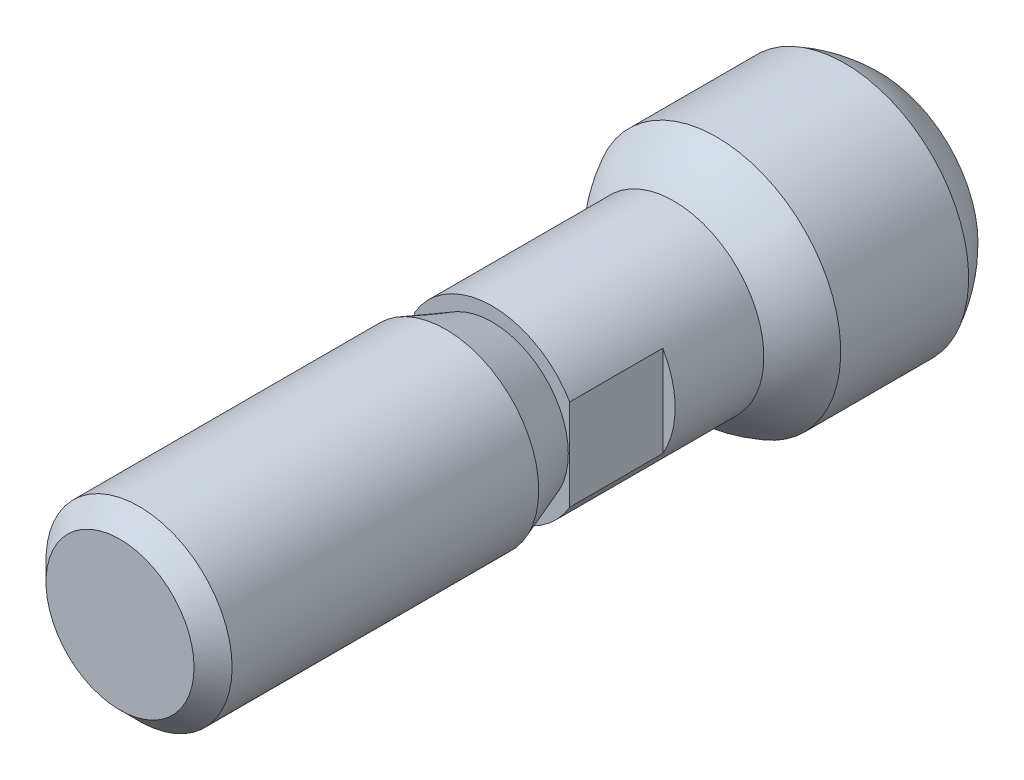
SolidWorks part; units mm, degrees
ref_plane "Ebene vorne" through (0, 0, 0) normal (0, 0, 1) x (1, 0, 0)
ref_plane "Ebene oben" through (0, 0, 0) normal (0, 1, 0) x (1, 0, 0)
ref_plane "Ebene rechts" through (0, 0, 0) normal (1, 0, 0) x (0, 0, -1)
sketch "Skizze1" plane through (0, 0, 0) normal (0, 1, 0) x (1, 0, 0)
  line L0 (0, 0) -> (-2.9, 0)
  line L1 (-2.9, 0) -> (-2.9, 5.8591)
  line L2 (-4, 7.2384) -> (-4, 11.3616)
  line L3 (-3.1639, 12.5) -> (0, 12.5)
  line L4 (0, 12.5) -> (0, 0)
  line L5 (0, 12.5) -> (0, 0) construction
  arc A0 (-2.9, 5.8591) -> (-4, 7.2384) centre (0, 9.3) cw
  arc A1 (-4, 11.3616) -> (-3.1639, 12.5) centre (0, 9.3) cw
revolve "Rotation1" add sketch "Skizze1" angle 360 about L5 reverse direction yes
ref_plane "Ebene1" through (0, 0, 0) normal (0, 0, 1) x (1, 0, 0)
sketch "Skizze2" plane through (0, 0, 0) normal (0, 0, 1) x (1, 0, 0)
  line L0 (6, 4) -> (2.5, 4)
  line L1 (2.5, 4) -> (2.5, -5)
  line L2 (2.5, -5) -> (-2.5, -5)
  line L3 (-2.5, -5) -> (-2.5, 4)
  line L4 (-2.5, 4) -> (-6, 4)
  line L5 (-6, 4) -> (-6, -6)
  line L6 (-6, -6) -> (6, -6)
  line L7 (6, -6) -> (6, 4)
extrude "Schnitt-Linear austragen1" cut sketch "Skizze2" along normal blind 3 and the other way blind 3
sketch "Skizze3" plane through (0, 0, 0) normal (0, 1, 0) x (1, 0, 0)
  line L0 (0, -12) -> (-2.3865, -12)
  line L1 (-2.3865, -12) -> (-3, -11.3865)
  line L2 (-3, -11.3865) -> (-3, -1.5)
  line L3 (-3, -1.5) -> (-2.454, 0)
  line L4 (-2.454, 0) -> (0, 0)
  line L5 (0, 0) -> (0, -12)
  line L6 (0, 0) -> (0, -12) construction
revolve "Rotation2" add sketch "Skizze3" angle 360 about L6 reverse direction yes
cosmetic thread "Gewindedarstellung1" parameters "D1"=10.5, "D2"=4.773
ref_plane "Ebene2" through (0, 0, 3.2) normal (0, 0, 1) x (1, 0, 0)
ref_plane "Ebene3" through (0, 0, 3) normal (0, 0, 1) x (1, 0, 0)
ref_plane "FDT_CYLINDER XY" through (0, 0, 3.2) normal (0, 0, -1) x (-1, 0, 0)
ref_plane "FDT_CYLINDER XZ" through (0, 0, 0) normal (0, 1, 0) x (1, 0, 0)
ref_plane "FDT_CYLINDER YZ" through (0, 0, 0) normal (1, 0, 0) x (0, 0, -1)
ref_axis "FDT_CYLINDER X" through (-80.9, 0, 3.2) along (1, 0, 0)
ref_axis "FDT_CYLINDER Y" through (0, 50, 3.2) along (0, -1, 0)
ref_axis "FDT_CYLINDER Z" through (0, 0, -80.9) along (0, 0, 1)
sketch3d "FDT_CYLINDER"
  point P0 (0, 0, 3.2)
ref_plane "MUTTER XY" through (0, 0, 12) normal (0, 0, 1) x (1, 0, 0)
ref_plane "MUTTER XZ" through (0, 0, 0) normal (0, 1, 0) x (1, 0, 0)
ref_plane "MUTTER YZ" through (0, 0, 0) normal (-1, 0, 0) x (0, 0, 1)
ref_axis "MUTTER X" through (80.9, 0, 12) along (-1, 0, 0)
ref_axis "MUTTER Y" through (0, 50, 12) along (0, -1, 0)
ref_axis "MUTTER Z" through (0, 0, 80.9) along (0, 0, -1)
sketch3d "MUTTER"
  point P0 (0, 0, 12)
ref_plane "bolzen XY" through (0, 0, 0) normal (1, 0, 0) x (0, 0, -1)
ref_plane "bolzen XZ" through (0, 0, 0) normal (0, -1, 0) x (-1, 0, 0)
ref_plane "bolzen YZ" through (0, 0, -9.3) normal (0, 0, -1) x (-1, 0, 0)
ref_axis "bolzen X" through (0, 0, 80.9) along (0, 0, -1)
ref_axis "bolzen Y" through (0, -50, -9.3) along (0, 1, 0)
ref_axis "bolzen Z" through (80.9, 0, -9.3) along (-1, 0, 0)
sketch3d "bolzen"
  point P0 (0, 0, -9.3)
